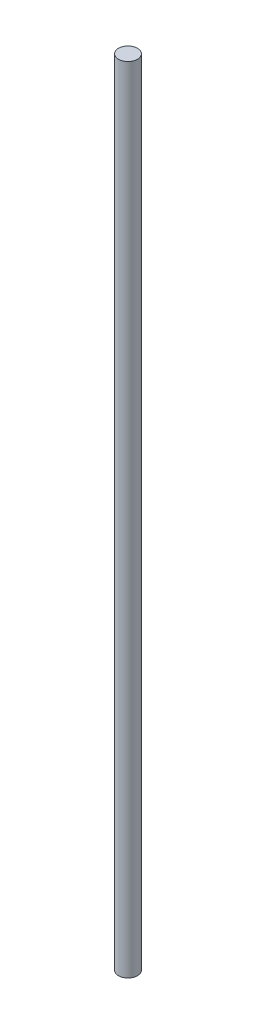
SolidWorks part; units mm, degrees
ref_plane "Front Plane" through (0, 0, 0) normal (0, 0, 1) x (1, 0, 0)
ref_plane "Top Plane" through (0, 0, 0) normal (0, 1, 0) x (1, 0, 0)
ref_plane "Right Plane" through (0, 0, 0) normal (1, 0, 0) x (0, 0, -1)
sketch "Sketch1" plane through (0, 0, 0) normal (0, 1, 0) x (1, 0, 0)
  circle A0 centre (0, 0) radius 4
  dimension "D1" = 8
extrude "Boss-Extrude1" add sketch "Sketch1" along normal up to surface (334 mm away)
